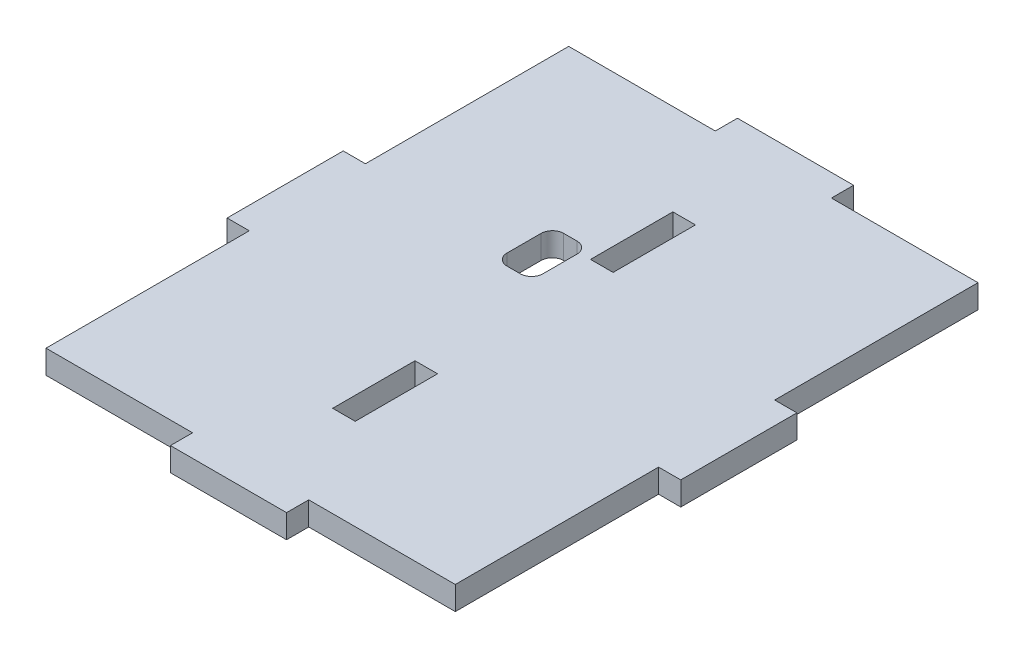
SolidWorks part; units mm, degrees
ref_plane "Front Plane" through (0, 0, 0) normal (0, 0, 1) x (1, 0, 0)
ref_plane "Top Plane" through (0, 0, 0) normal (0, 1, 0) x (1, 0, 0)
ref_plane "Right Plane" through (0, 0, 0) normal (1, 0, 0) x (0, 0, -1)
sketch "Sketch1" plane through (0, 0, 0) normal (0, 1, 0) x (1, 0, 0)
  line L1 (-40, 50) -> (40, 50)
  line L2 (-40, 50) -> (-40, -50)
  line L3 (-40, -50) -> (40, -50)
  line L4 (40, 50) -> (40, -50)
  line L5 (-40, 50) -> (40, -50) construction
  line L6 (-40, -50) -> (40, 50) construction
  point P0 (0, 0)
  dimension "Length" = 80
  dimension "with" = 100
extrude "Boss-Extrude1" add sketch "Sketch1" along normal blind 4.15
sketch "Sketch3" [suppressed] plane through (0, 4.15, 0) normal (0, 1, 0) x (1, 0, 0)
  line L0 (-100, 46.09) -> (-100, 50)
  line L1 (-100, -50) -> (-80.48, -50)
  line L2 (-100, -50) -> (-100, -46.09)
  line L3 (-100, -46.09) -> (-80.48, -46.09)
  line L4 (-80.48, -50) -> (-80.48, -46.09)
  line L5 (-100, 46.09) -> (-80.48, 46.09)
  line L6 (-80.48, 46.09) -> (-80.48, 50)
  line L7 (-100, 50) -> (-80.48, 50)
  line L8 (-60, 46.09) -> (-60, 50)
  line L9 (-60, 46.09) -> (-40.48, 46.09)
  line L10 (-40.48, 46.09) -> (-40.48, 50)
  line L11 (-60, 50) -> (-40.48, 50)
  line L12 (-20, 46.09) -> (-20, 50)
  line L13 (-20, 46.09) -> (-0.48, 46.09)
  line L14 (-0.48, 46.09) -> (-0.48, 50)
  line L15 (-20, 50) -> (-0.48, 50)
  line L16 (20, 46.09) -> (20, 50)
  line L17 (20, 46.09) -> (39.52, 46.09)
  line L18 (39.52, 46.09) -> (39.52, 50)
  line L19 (20, 50) -> (39.52, 50)
  line L20 (60, 46.09) -> (60, 50)
  line L21 (60, 46.09) -> (79.52, 46.09)
  line L22 (79.52, 46.09) -> (79.52, 50)
  line L23 (60, 50) -> (79.52, 50)
  line L24 (-60, -50) -> (-60, -46.09)
  line L25 (-60, -50) -> (-40.48, -50)
  line L26 (-40.48, -50) -> (-40.48, -46.09)
  line L27 (-60, -46.09) -> (-40.48, -46.09)
  line L28 (-20, -50) -> (-20, -46.09)
  line L29 (-20, -50) -> (-0.48, -50)
  line L30 (-0.48, -50) -> (-0.48, -46.09)
  line L31 (-20, -46.09) -> (-0.48, -46.09)
  line L32 (20, -50) -> (20, -46.09)
  line L33 (20, -50) -> (39.52, -50)
  line L34 (39.52, -50) -> (39.52, -46.09)
  line L35 (20, -46.09) -> (39.52, -46.09)
  line L36 (60, -50) -> (60, -46.09)
  line L37 (60, -50) -> (79.52, -50)
  line L38 (79.52, -50) -> (79.52, -46.09)
  line L39 (60, -46.09) -> (79.52, -46.09)
  line L40 (-100, -50) -> (100, -50) construction
  line L41 (100, 50) -> (-100, 50) construction
  point P5 (-80.48, -48.045)
  dimension "D1" = 3.91
  dimension "D2" = 19.52
  dimension "D5" = 20.48
  dimension "D3" = 2
  dimension "D4" = 5
extrude "Cut-Extrude2" [suppressed] cut sketch "Sketch3" against normal blind 10
sketch "Sketch4" [suppressed] plane through (0, 4.15, 0) normal (0, 1, 0) x (1, 0, 0)
  line L0 (-100, 9.76) -> (-100, -9.76)
  line L1 (-100, 9.76) -> (-96.09, 9.76)
  line L2 (-100, -9.76) -> (-96.09, -9.76)
  line L3 (-96.09, 9.76) -> (-96.09, -9.76)
  line L4 (-100, 46.09) -> (-100, -46.09) construction
  line L5 (0, -2.2825) -> (0, 2.2825) construction
  line L6 (100, -9.76) -> (96.09, -9.76)
  line L7 (96.09, 9.76) -> (96.09, -9.76)
  line L8 (100, 9.76) -> (96.09, 9.76)
  line L9 (100, 9.76) -> (100, -9.76)
  point P6 (-100, 0)
  dimension "D1" = 19.52
  dimension "D2" = 3.91
extrude "Cut-Extrude3" [suppressed] cut sketch "Sketch4" against normal blind 10
sketch "Sketch5" [suppressed] plane through (0, 4.15, 0) normal (0, 1, 0) x (1, 0, 0)
  line L0 (100, -36.09) -> (100, -40)
  line L1 (100, -36.09) -> (80.48, -36.09)
  line L2 (100, -40) -> (80.48, -40)
  line L3 (80.48, -36.09) -> (80.48, -40)
  line L4 (100, -40) -> (100, -9.76) construction
  line L5 (60, -36.09) -> (60, -40)
  line L6 (60, -36.09) -> (40.48, -36.09)
  line L7 (40.48, -36.09) -> (40.48, -40)
  line L8 (60, -40) -> (40.48, -40)
  line L9 (20, -36.09) -> (20, -40)
  line L10 (20, -36.09) -> (0.48, -36.09)
  line L11 (0.48, -36.09) -> (0.48, -40)
  line L12 (20, -40) -> (0.48, -40)
  line L13 (-20, -36.09) -> (-20, -40)
  line L14 (-20, -36.09) -> (-39.52, -36.09)
  line L15 (-39.52, -36.09) -> (-39.52, -40)
  line L16 (-20, -40) -> (-39.52, -40)
  line L17 (-60, -36.09) -> (-60, -40)
  line L18 (-60, -36.09) -> (-79.52, -36.09)
  line L19 (-79.52, -36.09) -> (-79.52, -40)
  line L20 (-60, -40) -> (-79.52, -40)
  line L21 (60, 40) -> (60, 36.09)
  line L22 (60, 40) -> (40.48, 40)
  line L23 (40.48, 40) -> (40.48, 36.09)
  line L24 (60, 36.09) -> (40.48, 36.09)
  line L25 (20, 40) -> (20, 36.09)
  line L26 (20, 40) -> (0.48, 40)
  line L27 (0.48, 40) -> (0.48, 36.09)
  line L28 (20, 36.09) -> (0.48, 36.09)
  line L29 (-20, 40) -> (-20, 36.09)
  line L30 (-20, 40) -> (-39.52, 40)
  line L31 (-39.52, 40) -> (-39.52, 36.09)
  line L32 (-20, 36.09) -> (-39.52, 36.09)
  line L33 (-60, 40) -> (-60, 36.09)
  line L34 (-60, 40) -> (-79.52, 40)
  line L35 (-79.52, 40) -> (-79.52, 36.09)
  line L36 (-60, 36.09) -> (-79.52, 36.09)
  line L37 (100, 40) -> (100, 36.09)
  line L38 (100, 40) -> (80.48, 40)
  line L39 (80.48, 40) -> (80.48, 36.09)
  line L40 (100, 36.09) -> (80.48, 36.09)
  line L41 (100, 40) -> (-100, 40) construction
  point P9 (100, 38.045)
  point P46 (100, -38.045)
  dimension "D1" = 3.91
  dimension "D2" = 19.52
  dimension "D5" = 20.48
  dimension "D3" = 5
  dimension "D4" = 2
extrude "Cut-Extrude4" [suppressed] cut sketch "Sketch5" against normal blind 10
sketch "Sketch6" plane through (0, 4.15, 0) normal (0, 1, 0) x (1, 0, 0)
  line L4 (-2.2825, 0) -> (2.2825, 0) construction
  line L5 (-40, -50) -> (-10.24, -50)
  line L6 (-40, -50) -> (-40, -46.09)
  line L7 (-40, -46.09) -> (-10.24, -46.09)
  line L8 (-10.24, -50) -> (-10.24, -46.09)
  line L9 (40, -50) -> (10.24, -50)
  line L10 (40, -50) -> (40, -46.09)
  line L11 (40, -46.09) -> (10.24, -46.09)
  line L12 (10.24, -50) -> (10.24, -46.09)
  line L13 (-40, 46.09) -> (-10.24, 46.09)
  line L14 (-10.24, 50) -> (-10.24, 46.09)
  line L15 (-40, 50) -> (-10.24, 50)
  line L16 (-40, 50) -> (-40, 46.09)
  line L17 (40, 46.09) -> (10.24, 46.09)
  line L18 (10.24, 50) -> (10.24, 46.09)
  line L19 (40, 50) -> (10.24, 50)
  line L20 (40, 50) -> (40, 46.09)
  line L21 (0, -2.2825) -> (0, 2.2825) construction
  line L22 (40, -46.09) -> (36.09, -46.09)
  line L23 (40, -46.09) -> (40, -10.24)
  line L24 (40, -10.24) -> (36.09, -10.24)
  line L25 (36.09, -46.09) -> (36.09, -10.24)
  line L26 (40, 46.09) -> (36.09, 46.09)
  line L27 (40, 46.09) -> (40, 10.24)
  line L28 (40, 10.24) -> (36.09, 10.24)
  line L29 (36.09, 46.09) -> (36.09, 10.24)
  line L30 (-40, 10.24) -> (-36.09, 10.24)
  line L31 (-36.09, 46.09) -> (-36.09, 10.24)
  line L32 (-40, 46.09) -> (-36.09, 46.09)
  line L33 (-40, 46.09) -> (-40, 10.24)
  line L34 (-40, -10.24) -> (-36.09, -10.24)
  line L35 (-36.09, -46.09) -> (-36.09, -10.24)
  line L36 (-40, -46.09) -> (-36.09, -46.09)
  line L37 (-40, -46.09) -> (-40, -10.24)
  line M21 (40, -50) -> (40, 50)
  line M22 (40, 50) -> (-40, 50)
  line M23 (-40, 50) -> (-40, -50)
  line M24 (-40, -50) -> (40, -50)
  dimension "D1" = 20.48
  dimension "D2" = 3.91
  dimension "D4" = 29.76
  dimension "D5" = 3.91
  dimension "D6" = 3.91
  dimension "D7" = 20.48
extrude "Cut-Extrude5" cut sketch "Sketch6" against normal blind 10 contours L12 L11 M24 M21 | L25 L11 L24 M21 | L17 L29 L28 M21 | L18 L17 M22 M21 | L14 L13 M22 M23 | L31 L13 L30 M23 | L7 L35 L34 M23 | L8 L7 M24 M23 region at (-25.12, 4.15, 48.045) region at (-38.045, 4.15, 28.165) region at (25.12, 4.15, 48.045) region at (-38.045, 4.15, -28.165) region at (38.045, 4.15, 28.165) region at (-25.12, 4.15, -48.045) region at (38.045, 4.15, -28.165) region at (25.12, 4.15, -48.045)
sketch "Sketch7" [suppressed] plane through (0, 4.15, 0) normal (0, 1, 0) x (1, 0, 0)
  line L0 (39.52, -46.09) -> (20, -46.09) construction
  line L1 (18.8, 13.91) -> (90, 13.91)
  line L2 (18.8, 13.91) -> (18.8, 37.91)
  line L3 (18.8, 37.91) -> (90, 37.91)
  line L4 (90, 13.91) -> (90, 37.91)
  line L5 (100, -50) -> (100, -9.76) construction
  dimension "D1" = 71.2
  dimension "D2" = 24
  dimension "D3" = 60
  dimension "D4" = 10
extrude "Cut-Extrude6" [suppressed] cut sketch "Sketch7" against normal blind 10
sketch "Sketch8" [suppressed] plane through (0, 4.15, 0) normal (0, 1, 0) x (1, 0, 0)
  line L0 (18.8, 37.91) -> (18.8, 13.91) construction
  line L1 (90, 13.91) -> (90, 37.91) construction
  line L4 (90, 37.91) -> (18.8, 37.91) construction
  line L5 (18.8, 13.91) -> (90, 13.91) construction
  circle A0 centre (16.9, 10.16) radius 1.5
  circle A1 centre (16.9, 41.66) radius 1.5
  circle A2 centre (91.9, 41.66) radius 1.5
  circle A3 centre (91.9, 10.16) radius 1.5
  dimension "D1" = 2
  dimension "D3" = 3
  dimension "D7" = 1.9
  dimension "D4" = 3.75
  dimension "D5" = 3.75
  dimension "D6" = 1.9
  dimension "D2" = 2
extrude "Cut-Extrude7" [suppressed] cut sketch "Sketch8" against normal blind 10
sketch "Sketch9" [suppressed] plane through (0, 4.15, 0) normal (0, 1, 0) x (1, 0, 0)
  line L0 (-0.48, -46.09) -> (-20, -46.09) construction
  line L1 (8.8, 3.91) -> (5.4, 3.91)
  line L2 (8.8, 3.91) -> (8.8, 42.91)
  line L3 (8.8, 42.91) -> (5.4, 42.91)
  line L4 (5.4, 3.91) -> (5.4, 42.91)
  line L5 (18.8, 37.91) -> (18.8, 13.91) construction
  dimension "D1" = 3.4
  dimension "D2" = 39
  dimension "D3" = 50
  dimension "D4" = 10
extrude "Cut-Extrude8" [suppressed] cut sketch "Sketch9" against normal blind 10
sketch "Sketch10" [suppressed] plane through (0, 4.15, 0) normal (0, 1, 0) x (1, 0, 0)
  line L1 (96.09, 9.76) -> (96.09, -9.76) construction
  line L3 (39.52, -46.09) -> (20, -46.09) construction
  circle A0 centre (26.09, -1.09) radius 3.425
  dimension "D1" = 6.85
  dimension "D2" = 45
  dimension "D3" = 70
extrude "Cut-Extrude9" [suppressed] cut sketch "Sketch10" against normal blind 10 contours A0
sketch "Sketch11" [suppressed] plane through (0, 4.15, 0) normal (0, 1, 0) x (1, 0, 0)
  line L1 (96.09, 9.76) -> (96.09, -9.76) construction
  line L4 (39.52, -46.09) -> (20, -46.09) construction
  circle A0 centre (41.09, -1.09) radius 3.125
  circle A1 centre (53.09, -1.09) radius 3.125
  dimension "D1" = 6.25
  dimension "D3" = 55
  dimension "D5" = 12
  dimension "D2" = 45
  dimension "D4" = 2
extrude "Cut-Extrude10" [suppressed] cut sketch "Sketch11" against normal blind 10
sketch "Sketch12" [suppressed] plane through (0, 4.15, 0) normal (0, 1, 0) x (1, 0, 0)
  line L1 (96.09, 9.76) -> (96.09, -9.76) construction
  line L2 (79.52, -46.09) -> (60, -46.09) construction
  circle A0 centre (68.09, -1.09) radius 3.825
  circle A1 centre (81.09, -1.09) radius 3.825
  dimension "D1" = 7.65
  dimension "D2" = 45
  dimension "D4" = 28
  dimension "D5" = 15
  dimension "D6" = 45
  dimension "D3" = 2
sketch "Sketch13" [suppressed] plane through (0, 4.15, 0) normal (0, 1, 0) x (1, 0, 0)
  line L0 (100, -50) -> (100, 50) construction
  line L1 (24.76, 50) -> (-24.76, 50)
  line L3 (24.76, 45.78) -> (-24.76, 45.78)
  line L4 (-24.76, 50) -> (-24.76, 45.78)
  line L5 (0, -2.2825) -> (0, 2.2825) construction
  line L6 (-100, 50) -> (-50.24, 50)
  line L8 (-95.78, 45.78) -> (-50.24, 45.78)
  line L9 (-50.24, 50) -> (-50.24, 45.78)
  line L10 (95.78, 45.78) -> (50.24, 45.78)
  line L11 (50.24, 50) -> (50.24, 45.78)
  line L12 (100, 50) -> (50.24, 50)
  line L14 (24.76, 50) -> (24.76, 45.78)
  line L15 (-100, 50) -> (-100, -50) construction
  line L21 (-100, -15.72) -> (-100, 15.72)
  line L22 (-100, 15.72) -> (-95.78, 15.72)
  line L23 (-95.78, -15.72) -> (-95.78, 15.72)
  line L24 (-2.2825, 0) -> (2.2825, 0) construction
  line L26 (-100, 50) -> (-100, 30.24)
  line L27 (-100, 30.24) -> (-95.78, 30.24)
  line L28 (-95.78, 45.78) -> (-95.78, 30.24)
  line L29 (-100, -15.72) -> (-95.78, -15.72)
  line L30 (-100, -30.24) -> (-95.78, -30.24)
  line L31 (-95.78, -50) -> (-95.78, -30.24)
  line L32 (-100, -50) -> (-95.78, -50)
  line L33 (-100, -50) -> (-100, -30.24)
  line L34 (100, 30.24) -> (95.78, 30.24)
  line L35 (95.78, 45.78) -> (95.78, 30.24)
  line L37 (100, 50) -> (100, 30.24)
  line L38 (100, -15.72) -> (100, 15.72)
  line L39 (100, 15.72) -> (95.78, 15.72)
  line L40 (95.78, -15.72) -> (95.78, 15.72)
  line L41 (100, -15.72) -> (95.78, -15.72)
  line L42 (100, -50) -> (100, -30.24)
  line L43 (100, -50) -> (95.78, -50)
  line L44 (95.78, -50) -> (95.78, -30.24)
  line L45 (100, -30.24) -> (95.78, -30.24)
  line L46 (-100, -50) -> (100, -50) construction
  line L47 (100, 50) -> (-100, 50) construction
  dimension "D1" = 4.22
  dimension "D2" = 49.76
  dimension "D3" = 25.48
  dimension "D4" = 4.22
  dimension "D5" = 19.76
  dimension "D6" = 4.22
  dimension "D7" = 4.22
  dimension "D8" = 14.52
  dimension "D9" = 31.44
extrude "Cut-Extrude12" [suppressed] cut sketch "Sketch13" against normal blind 10
sketch "Sketch14" [suppressed] plane through (0, 4.15, 0) normal (0, 1, 0) x (1, 0, 0)
  line L0 (95.78, -30.24) -> (95.78, -50) construction
  line L1 (-96.02, -50) -> (95.78, -50)
  line L2 (-96.02, -50) -> (-96.02, -45.78)
  line L3 (-96.02, -45.78) -> (95.78, -45.78)
  line L4 (95.78, -50) -> (95.78, -45.78)
  dimension "D1" = 4.22
extrude "Cut-Extrude13" [suppressed] cut sketch "Sketch14" against normal blind 10
sketch "Sketch15" plane through (0, 4.15, 0) normal (0, 1, 0) x (1, 0, 0)
  line L0 (10.24, 50) -> (-10.24, 50) construction
  line L1 (2.35, 30) -> (-1.63, 30)
  line L2 (2.35, 30) -> (2.35, 15.48)
  line L3 (2.35, 15.48) -> (-1.63, 15.48)
  line L4 (-1.63, 30) -> (-1.63, 15.48)
  line L5 (2.35, 30) -> (-1.63, 15.48) construction
  line L6 (2.35, 15.48) -> (-1.63, 30) construction
  line L7 (36.09, 46.09) -> (36.09, 10.24) construction
  line L9 (-2.2825, 0) -> (2.2825, 0) construction
  line L10 (2.35, -15.48) -> (-1.63, -15.48)
  line L11 (-1.63, -30) -> (-1.63, -15.48)
  line L12 (2.35, -30) -> (-1.63, -30)
  line L13 (2.35, -30) -> (2.35, -15.48)
  point P0 (0.36, 22.74)
  dimension "D1" = 20
  dimension "D2" = 14.52
  dimension "D3" = 33.74
  dimension "D4" = 3.98
extrude "Cut-Extrude14" cut sketch "Sketch15" against normal blind 10
sketch "Sketch16" [suppressed] plane through (0, 4.15, 0) normal (0, 1, 0) x (1, 0, 0)
  line L1 (-25.24, 2.195) -> (-50.48, 2.195)
  line L2 (-25.24, 2.195) -> (-25.24, -2.195)
  line L3 (-25.24, -2.195) -> (-50.48, -2.195)
  line L4 (-50.48, 2.195) -> (-50.48, -2.195)
  line L5 (-25.24, 2.195) -> (-50.48, -2.195) construction
  line L6 (-25.24, -2.195) -> (-50.48, 2.195) construction
  line L8 (0, -2.2825) -> (0, 2.2825) construction
  line L9 (25.24, -2.195) -> (50.48, -2.195)
  line L10 (50.48, 2.195) -> (50.48, -2.195)
  line L11 (25.24, 2.195) -> (50.48, 2.195)
  line L12 (25.24, 2.195) -> (25.24, -2.195)
  line L13 (-25.24, -36.09) -> (-25.24, 36.09) construction
  line L14 (-20, -36.09) -> (-39.52, -36.09) construction
  line L15 (-39.52, 36.09) -> (-20, 36.09) construction
  line L16 (-100, 40) -> (-100, 9.76) construction
  point P0 (-37.86, 0)
  point P5 (-25.24, 0)
  point P6 (-25.24, 0)
  point P7 (25.24, 0)
  dimension "D1" = 4.39
  dimension "D2" = 49.52
  dimension "D3" = 25.24
extrude "Cut-Extrude15" [suppressed] cut sketch "Sketch16" against normal blind 10
sketch "Sketch18" [suppressed] plane through (0, 4.15, 0) normal (0, 1, 0) x (1, 0, 0)
  line L0 (95.78, 15.72) -> (95.78, -15.72) construction
  line L1 (12.78, 37.5) -> (22.78, 37.5)
  line L3 (7.78, -31.78) -> (22.78, -31.78)
  line L4 (22.78, 37.5) -> (22.78, -31.78)
  line L5 (7.78, 2.5) -> (7.78, -31.78)
  line L6 (12.78, 37.5) -> (-7.22, 37.5)
  line L10 (95.78, -45.78) -> (-95.78, -45.78) construction
  line L11 (-24.76, 45.78) -> (24.76, 45.78) construction
  line L14 (7.78, 2.5) -> (-7.22, 2.5)
  line L15 (-7.22, 37.5) -> (-7.22, 2.5)
  dimension "D1" = 15
  dimension "D2" = 8.28
  dimension "D3" = 73
  dimension "D4" = 14
  dimension "D6" = 35
  dimension "D7" = 15
extrude "Cut-Extrude18" [suppressed] cut sketch "Sketch18" against normal blind 10
sketch "Sketch19" [suppressed] plane through (0, 4.15, 0) normal (0, 1, 0) x (1, 0, 0)
  line L0 (5.4, 42.91) -> (5.4, 3.91) construction
  line L1 (-2.1, 25.91) -> (0.9, 25.91)
  line L2 (-2.1, 25.91) -> (-2.1, 20.91)
  line L3 (-2.1, 20.91) -> (0.9, 20.91)
  line L4 (0.9, 25.91) -> (0.9, 20.91)
  line L5 (-2.1, 25.91) -> (0.9, 20.91) construction
  line L6 (-2.1, 20.91) -> (0.9, 25.91) construction
  point P0 (-0.6, 23.41)
  point P7 (5.4, 23.41)
  point P8 (0.9, 23.41)
  dimension "D1" = 4.5
  dimension "D2" = 3
  dimension "D4" = 5
extrude "Cut-Extrude19" [suppressed] cut sketch "Sketch19" against normal blind 4.2
sketch "Sketch20" [suppressed] plane through (0, 4.15, 0) normal (0, 1, 0) x (1, 0, 0)
  line L0 (100, -30.24) -> (100, -15.72) construction
  line L1 (-1.85, -18.28) -> (1.15, -18.28)
  line L2 (-1.85, -18.28) -> (-1.85, -23.28)
  line L3 (-1.85, -23.28) -> (1.15, -23.28)
  line L4 (1.15, -18.28) -> (1.15, -23.28)
  line L5 (-1.85, -18.28) -> (1.15, -23.28) construction
  line L6 (-1.85, -23.28) -> (1.15, -18.28) construction
  line L8 (95.78, -45.78) -> (-95.78, -45.78) construction
  point P0 (-0.35, -20.78)
  dimension "D1" = 22.5
  dimension "D2" = 98.85
  dimension "D3" = 3
  dimension "D4" = 5
extrude "Cut-Extrude21" [suppressed] cut sketch "Sketch20" against normal blind 4.2
sketch "Sketch21" [suppressed] plane through (0, 4.15, 0) normal (0, 1, 0) x (1, 0, 0)
  line L0 (100, 9.76) -> (100, 50) construction
  line L1 (35.9, 25.91) -> (40.9, 25.91)
  line L2 (35.9, 25.91) -> (35.9, 20.91)
  line L3 (35.9, 20.91) -> (40.9, 20.91)
  line L4 (40.9, 25.91) -> (40.9, 20.91)
  line L5 (35.9, 25.91) -> (40.9, 20.91) construction
  line L6 (35.9, 20.91) -> (40.9, 25.91) construction
  line L7 (-100, 46.09) -> (-80.48, 46.09) construction
  line L9 (-84.59, 25.91) -> (-79.59, 25.91)
  line L10 (-84.59, 25.91) -> (-84.59, 20.91)
  line L11 (-84.59, 20.91) -> (-79.59, 20.91)
  line L12 (-79.59, 25.91) -> (-79.59, 20.91)
  line L13 (20, 46.09) -> (39.52, 46.09) construction
  point P0 (38.4, 23.41)
  dimension "D1" = 5
  dimension "D2" = 5
  dimension "D3" = 59.1
  dimension "D4" = 20.18
  dimension "D5" = 5
  dimension "D6" = 5
  dimension "D7" = 125.49
  dimension "D8" = 20.18
extrude "Cut-Extrude22" [suppressed] cut sketch "Sketch21" against normal blind 4.2
sketch "Sketch22" [suppressed] plane through (0, 4.15, 0) normal (0, 1, 0) x (1, 0, 0)
  line L1 (-24.76, 45.78) -> (24.76, 45.78) construction
  line L2 (-95.78, -15.72) -> (-95.78, 15.72) construction
  circle A0 centre (-78.55, -14.22) radius 1.5
  circle A1 centre (-5.55, -14.22) radius 1.5
  dimension "D1" = 3
  dimension "D2" = 3
  dimension "D3" = 73
  dimension "D4" = 17.23
  dimension "D5" = 60
extrude "Cut-Extrude23" [suppressed] cut sketch "Sketch22" against normal blind 10
extrude "Cut-Extrude24" [suppressed] cut sketch "Sketch12" against normal blind 10
sketch "Sketch23" [suppressed] plane through (0, 4.15, 0) normal (0, 1, 0) x (1, 0, 0)
  line L0 (-96.09, -9.76) -> (-96.09, 9.76) construction
  line L1 (32.91, 30.75) -> (-65.09, 30.75)
  line L2 (32.91, 30.75) -> (32.91, -30.75)
  line L3 (32.91, -30.75) -> (-65.09, -30.75)
  line L4 (-65.09, 30.75) -> (-65.09, -30.75)
  line L7 (-40.48, -46.09) -> (-60, -46.09) construction
  point P6 (-96.09, 0)
  dimension "D1" = 98
  dimension "D2" = 61.5
  dimension "D3" = 31
  dimension "D4" = 15.34
extrude "Cut-Extrude25" [suppressed] cut sketch "Sketch23" against normal blind 10
sketch "Sketch24" [suppressed] plane through (0, 4.15, 0) normal (0, 1, 0) x (1, 0, 0)
  line L0 (-100, -9.76) -> (-100, -46.09) construction
  line L2 (-80.48, -50) -> (-60, -50) construction
  circle A0 centre (-70.79, -21.8) radius 1.5
  dimension "D1" = 3
  dimension "D2" = 29.21
  dimension "D3" = 28.2
extrude "Cut-Extrude26" [suppressed] cut sketch "Sketch24" against normal blind 10
mirror "Mirror1" [suppressed] about plane through (0, 0, 0) normal (0, 0, 1)
sketch "Sketch25" [suppressed] plane through (0, 4.15, 0) normal (0, 1, 0) x (1, 0, 0)
  line L0 (50.24, 50) -> (24.76, 50) construction
  line L1 (22.78, -31.78) -> (22.78, 37.5) construction
  circle A0 centre (24.78, 20) radius 1.5
  circle A1 centre (24.78, -7.9) radius 1.5
  circle A2 centre (77.18, 25.1) radius 1.5
  circle A3 centre (75.58, -23.2) radius 1.5
  dimension "D1" = 3
  dimension "D2" = 27.9
  dimension "D3" = 50.8
  dimension "D4" = 15.3
  dimension "D8" = 2
  dimension "D5" = 52.4
  dimension "D6" = 48.3
  dimension "D7" = 30
extrude "Cut-Extrude27" [suppressed] cut sketch "Sketch25" against normal blind 10
sketch "Sketch26" plane through (0, 4.15, 0) normal (0, 1, 0) x (1, 0, 0)
  line L0 (-36.09, 46.09) -> (-10.24, 46.09) construction
  line L1 (-9.97, 17.09) -> (-3.63, 17.09)
  line L2 (-9.97, 17.09) -> (-9.97, 7.09)
  line L3 (-9.97, 7.09) -> (-3.63, 7.09)
  line L4 (-3.63, 17.09) -> (-3.63, 7.09)
  line L5 (-1.63, 30) -> (-1.63, 15.48) construction
  dimension "D1" = 6.34
  dimension "D2" = 10
  dimension "D3" = 29
  dimension "D4" = 2
extrude "Cut-Extrude28" cut sketch "Sketch26" against normal blind 10
fillet "Fillet1" radius 2 4 edges at (-9.97, 2.075, -17.09) (-3.63, 2.075, -17.09) (-9.97, 2.075, -7.09) (-3.63, 2.075, -7.09)
equation "\"kerf\"=0.24"
equation "\"D5@Sketch5\"=20 + 2*\"kerf\""
